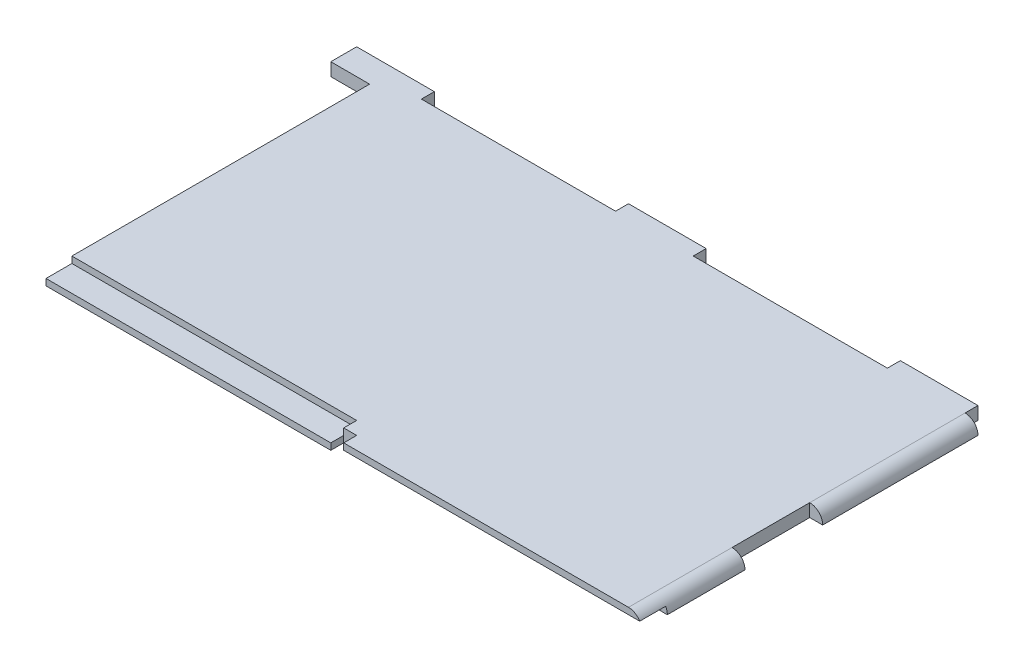
SolidWorks part; units mm, degrees
ref_plane "前基準面" through (0, 0, 0) normal (0, 0, 1) x (1, 0, 0)
ref_plane "上基準面" through (0, 0, 0) normal (0, 1, 0) x (1, 0, 0)
ref_plane "右基準面" through (0, 0, 0) normal (1, 0, 0) x (0, 0, -1)
sketch "草圖1" plane through (0, 0, 0) normal (0, 1, 0) x (1, 0, 0)
  line L0 (-36.2537, 43.5351) -> (203.7463, 43.5351)
  line L1 (203.7463, 43.5351) -> (203.7463, -286.4649)
  line L2 (198.7463, -286.4649) -> (198.7463, -256.4649)
  line L3 (198.7463, -256.4649) -> (183.2463, -256.4649)
  line L4 (183.2463, -256.4649) -> (183.2463, -266.4649)
  line L5 (183.2463, -266.4649) -> (124.7463, -266.4649)
  line L6 (124.7463, -266.4649) -> (124.7463, -262.4649)
  line L7 (124.7463, -262.4649) -> (109.2463, -262.4649)
  line L8 (109.2463, -262.4649) -> (109.2463, -266.4649)
  line L9 (109.2463, -266.4649) -> (-21.2537, -266.4649)
  line L10 (-21.2537, -266.4649) -> (-21.2537, 38.5351)
  line L11 (-21.2537, 38.5351) -> (-36.2537, 38.5351)
  line L12 (-36.2537, 38.5351) -> (-36.2537, 43.5351)
  line L13 (198.7463, -286.4649) -> (203.7463, -286.4649)
  line L15 (203.7463, -286.4649) -> (208.7463, -286.4649)
  line L16 (203.7463, -286.4649) -> (203.7463, -226.4649)
  line L17 (203.7463, -226.4649) -> (208.7463, -226.4649)
  line L18 (208.7463, -286.4649) -> (208.7463, -226.4649)
  line L19 (-36.2537, 43.5351) -> (-6.2537, 43.5351)
  line L20 (-36.2537, 43.5351) -> (-36.2537, 48.5351)
  line L21 (-36.2537, 48.5351) -> (-6.2537, 48.5351)
  line L22 (-6.2537, 43.5351) -> (-6.2537, 48.5351)
  line L23 (203.7463, 43.5351) -> (173.7463, 43.5351)
  line L24 (203.7463, 43.5351) -> (203.7463, 48.5351)
  line L25 (203.7463, 48.5351) -> (173.7463, 48.5351)
  line L26 (173.7463, 43.5351) -> (173.7463, 48.5351)
  line L27 (203.7463, 43.5351) -> (208.7463, 43.5351)
  line L28 (203.7463, 43.5351) -> (203.7463, -16.4649)
  line L29 (203.7463, -16.4649) -> (208.7463, -16.4649)
  line L30 (208.7463, 43.5351) -> (208.7463, -16.4649)
  line L31 (83.7463, 43.5351) -> (98.7463, 43.5351)
  line L32 (83.7463, 43.5351) -> (83.7463, 48.5351)
  line L33 (83.7463, 48.5351) -> (98.7463, 48.5351)
  line L34 (98.7463, 43.5351) -> (98.7463, 48.5351)
  line L35 (83.7463, 43.5351) -> (68.7463, 43.5351)
  line L36 (83.7463, 43.5351) -> (83.7463, 48.5351)
  line L37 (83.7463, 48.5351) -> (68.7463, 48.5351)
  line L38 (68.7463, 43.5351) -> (68.7463, 48.5351)
  line L39 (203.7463, -46.4649) -> (208.7463, -46.4649)
  line L40 (203.7463, -46.4649) -> (203.7463, -106.4649)
  line L41 (203.7463, -106.4649) -> (208.7463, -106.4649)
  line L42 (208.7463, -46.4649) -> (208.7463, -106.4649)
  line L43 (203.7463, -136.4649) -> (208.7463, -136.4649)
  line L44 (203.7463, -136.4649) -> (203.7463, -196.4649)
  line L45 (203.7463, -196.4649) -> (208.7463, -196.4649)
  line L46 (208.7463, -136.4649) -> (208.7463, -196.4649)
  dimension "D3" = 5
  dimension "D1" = 240
  dimension "D2" = 330
  dimension "D4" = 15
  dimension "D5" = 130.5
  dimension "D6" = 4
  dimension "D7" = 4
  dimension "D8" = 15.5
  dimension "D9" = 58.5
  dimension "D10" = 10
  dimension "D11" = 15.5
  dimension "D12" = 30
  dimension "D13" = 5
  dimension "D14" = 60
  dimension "D15" = 5
  dimension "D16" = 5
  dimension "D17" = 30
  dimension "D18" = 5
  dimension "D19" = 30
  dimension "D20" = 60
  dimension "D21" = 5
  dimension "D22" = 5
  dimension "D23" = 15
  dimension "D24" = 5
  dimension "D25" = 15
  dimension "D26" = 60
  dimension "D27" = 5
  dimension "D28" = 30
  dimension "D29" = 60
  dimension "D30" = 5
  dimension "D31" = 30
  dimension "D32" = 30
extrude "填料-伸長1" add sketch "草圖1" along normal blind 5 contours L2 L13 L1 L0 L12 L11 L10 L9 L8 L7 L6 L5 L4 L3 | L15 L18 L17 L1 | L30 L27 L1 L29 | L26 L0 L24 L25 | L0 L22 L21 L20 | L32 L33 L34 L31 | L36 L37 L38 L35 | L46 L45 L44 L43 | L42 L41 L40 L39 region at (-21.2537, 0, -46.0351) region at (91.0303, 0, 111.0679) region at (188.7463, 0, -46.0351) region at (206.2463, 0, -13.5351) region at (206.2463, 0, 256.4649)
fillet "圓角1" radius 5 4 edges at (208.7463, 5, -13.5351) (208.7463, 5, 76.4649) (208.7463, 5, 166.4649) (208.7463, 5, 256.4649)
sketch "草圖2" plane through (0, 5, 0) normal (0, 1, 0) x (1, 0, 0)
  line L0 (208.7463, -136.4649) -> (203.7463, -136.4649) construction
  line L1 (208.7463, -86.4649) -> (-30.7437, -86.4649)
  line L2 (208.7463, -86.4649) -> (208.7463, -299.5734)
  line L3 (208.7463, -299.5734) -> (-30.7437, -299.5734)
  line L4 (-30.7437, -86.4649) -> (-30.7437, -299.5734)
  dimension "D1" = 50
extrude "除料-伸長2" cut sketch "草圖2" against normal blind 10
sketch "草圖3" plane through (0, 0, 86.4649) normal (0, 0, 1) x (1, 0, 0)
  line L0 (-21.2537, 5) -> (-21.2537, 0) construction
  line L1 (-21.2537, 2.5) -> (88.7463, 2.5)
  line L2 (-21.2537, 2.5) -> (-21.2537, 5)
  line L3 (-21.2537, 5) -> (88.7463, 5)
  line L4 (88.7463, 2.5) -> (88.7463, 5)
  line L6 (93.7463, 2.5) -> (208.7463, 2.5)
  line L7 (93.7463, 2.5) -> (93.7463, 0)
  line L8 (93.7463, 0) -> (208.7463, 0)
  line L9 (208.7463, 2.5) -> (208.7463, 0)
  dimension "D1" = 2.5
  dimension "D2" = 110
  dimension "D3" = 115
  dimension "D4" = 2.5
extrude "除料-伸長3" cut sketch "草圖3" against normal blind 10
sketch "草圖4" plane through (0, 0, 86.4649) normal (0, 0, 1) x (1, 0, 0)
  line L1 (88.7463, 5) -> (93.7463, 5)
  line L2 (88.7463, 5) -> (88.7463, 0)
  line L3 (88.7463, 0) -> (93.7463, 0)
  line L4 (93.7463, 5) -> (93.7463, 0)
extrude "除料-伸長4" cut sketch "草圖4" against normal blind 5
